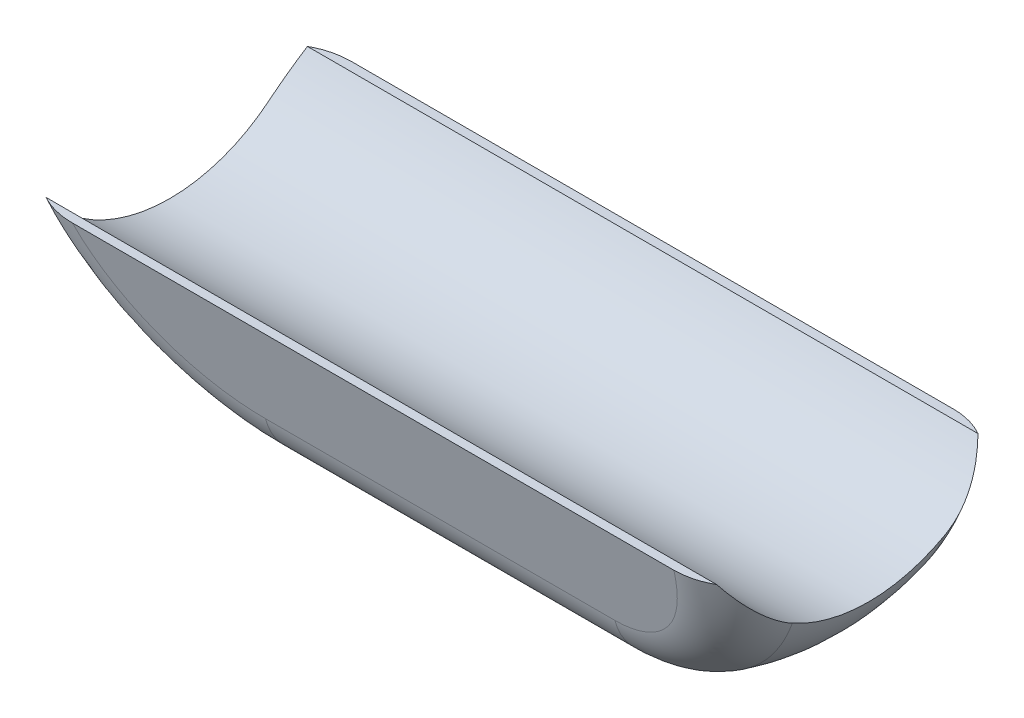
SolidWorks part; units mm, degrees
ref_plane "Front Plane" through (0, 0, 0) normal (0, 0, 1) x (1, 0, 0)
ref_plane "Top Plane" through (0, 0, 0) normal (0, 1, 0) x (1, 0, 0)
ref_plane "Right Plane" through (0, 0, 0) normal (1, 0, 0) x (0, 0, -1)
sketch "Sketch1" plane through (0, 0, 0) normal (0, 0, 1) x (1, 0, 0)
  line L0 (-397.4275, 0) -> (453.9338, 0) construction
  line L1 (-63.5, -88.9) -> (63.5, -88.9)
  line L2 (-159.945, -57.15) -> (233.084, -57.15) construction
  line L3 (-139.7, -57.15) -> (114.3, -57.15)
  arc A0 (63.5, -88.9) -> (114.3, -57.15) centre (63.5, -32.385) ccw
  arc A1 (-63.5, -88.9) -> (-139.7, -57.15) centre (-63.5, 18.415) cw
  dimension "D1" = 127
  dimension "D2" = 57.15
  dimension "D3" = 88.9
  dimension "D4" = 76.2
  dimension "D5" = 50.8
  dimension "D6" = 63.5
revolve "Revolve1" add sketch "Sketch1" angle 90 about L0
sketch "Sketch3" plane through (0, 0, 0) normal (1, 0, 0) x (0, 0, -1)
  line L0 (-55.2975, -14.433) -> (-38.1, -80.3219)
  line L1 (55.2975, -14.433) -> (38.1, -80.3219)
  line L2 (-55.2975, -14.433) -> (-36.1428, 7.1135)
  line L3 (-36.1428, 7.1135) -> (-91.2525, 13.8917)
  line L4 (-91.2525, 13.8917) -> (-85.8297, -64.2712)
  line L5 (-85.8297, -64.2712) -> (-38.1, -80.3219)
  line L6 (55.2975, -14.433) -> (44.836, -5.1329)
  line L7 (44.836, -5.1329) -> (61.253, 13.3343)
  line L8 (61.253, 13.3343) -> (115.9355, 3.0462)
  line L9 (115.9355, 3.0462) -> (83.3988, -75.4908)
  line L10 (83.3988, -75.4908) -> (38.1, -80.3219)
  arc A0 (-57.15, 0) -> (57.15, 0) centre (0, 0) ccw construction
  arc A1 (-88.9, 0) -> (88.9, 0) centre (0, 0) ccw construction
  point P18 (-32.7869, 4.1301)
  dimension "D1" = 38.1
  dimension "D2" = 38.1
extrude "Cut-Extrude1" cut sketch "Sketch3" against normal through all and the other way through all
fillet "Fillet1" radius 25.4 6 edges at (-114.1055, -63.2286, -42.5615) (0, -80.3219, -38.1) (-114.0781, -63.25, 42.5559) (0, -80.3219, 38.1) (101.2726, -60.5599, -43.258) (91.4599, -70.6527, 40.6237)
sketch "Sketch5" plane through (0, 0, 0) normal (1, 0, 0) x (0, 0, -1)
  line L1 (57.1316, -82.55) -> (-57.1316, -82.55) construction
  line L2 (57.1316, -82.55) -> (57.1316, -31.75) construction
  line L3 (57.1316, -31.75) -> (-57.1316, -31.75) construction
  line L4 (-57.1316, -82.55) -> (-57.1316, -31.75) construction
  line L5 (57.1316, -82.55) -> (-57.1316, -31.75) construction
  line L6 (57.1316, -31.75) -> (-57.1316, -82.55) construction
  arc A0 (-27.7031, -49.9866) -> (27.7031, -49.9866) centre (0, 0) ccw construction
  point P0 (0, -57.15)
  point P5 (-0.8907, -75.84)
  point P6 (0, -71.5138)
  point P7 (0, -63.752)
  point P8 (-1.5269, -69.3507)
  point P9 (0, 0)
  point P10 (0, -51.5368)
  point P11 (-2.5448, -69.8596)
  point P12 (0, 0)
  point P13 (-0.7653, -57.1449)
  point P17 (0, -57.15)
  point P18 (-57.1316, -82.55)
  dimension "D1" = 50.8
  dimension "D2" = 114.2633
sketch "Sketch6" plane through (0, 0, 0) normal (1, 0, 0) x (0, 0, -1)
  line L0 (57.1316, -82.55) -> (-57.1316, -82.55) construction
  line L1 (59.6453, 31.75) -> (-59.6453, 31.75)
  line L2 (59.6453, 31.75) -> (59.6453, -31.75)
  line L3 (59.6453, -31.75) -> (-59.6453, -31.75)
  line L4 (-59.6453, 31.75) -> (-59.6453, -31.75)
  line L5 (59.6453, 31.75) -> (-59.6453, -31.75) construction
  line L6 (59.6453, -31.75) -> (-59.6453, 31.75) construction
  point P0 (0, 0)
  dimension "D1" = 50.8
extrude "Cut-Extrude2" cut sketch "Sketch6" against normal through all and the other way through all
